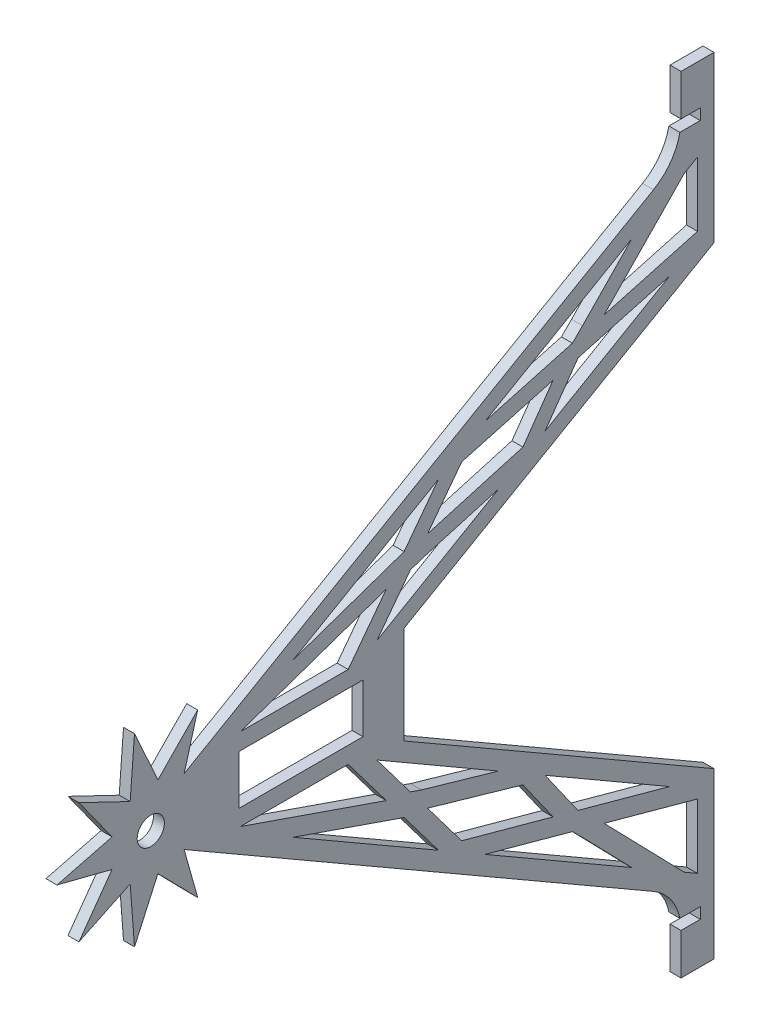
SolidWorks part; units mm, degrees
ref_plane "Front Plane" through (0, 0, 0) normal (1, 0, 0) x (0, 1, 0)
ref_plane "Top Plane" through (0, 0, 0) normal (0, 0, 1) x (0, 1, 0)
ref_plane "Right Plane" through (0, 0, 0) normal (0, 1, 0) x (-1, 0, 0)
sketch "Sketch1" plane through (0, 0, 0) normal (1, 0, 0) x (0, 1, 0)
  line L0 (-4.95, 0) -> (-129.0803, -215) construction
  line L1 (0, -4.95) -> (-121.2724, -215) construction
  line L2 (0, -4.95) -> (121.2724, -215) construction
  line L3 (4.95, 0) -> (129.0803, -215) construction
  line L4 (0, 0) -> (0, -215) construction
  line L5 (-129.0803, -215) -> (129.0803, -215) construction
  line L6 (0, 0) -> (0, -38.94) construction
  line L7 (0, -38.94) -> (0, -77.24) construction
  line L8 (-8.95, -32.14) -> (8.95, -32.14)
  line L9 (-8.95, -32.14) -> (-8.95, -77.24)
  line L10 (-8.95, -77.24) -> (8.95, -77.24)
  line L11 (8.95, -32.14) -> (8.95, -77.24)
  line L12 (-10.8997, -10.3052) -> (-129.0803, -215)
  line L13 (-129.0803, -215) -> (-88.6658, -215)
  line L14 (-88.6658, -215) -> (-17.7903, -92.24)
  line L15 (-17.7903, -92.24) -> (17.7903, -92.24)
  line L16 (17.7903, -92.24) -> (88.6658, -215)
  line L17 (88.6658, -215) -> (129.0803, -215)
  line L18 (129.0803, -215) -> (10.8997, -10.3052)
  circle A0 centre (0, 0) radius 4.95 construction
  circle A1 centre (0, 0) radius 7.5 construction
  arc A2 (-10.8997, -10.3052) -> (10.8997, -10.3052) centre (0, 0) cw
  circle A3 centre (0, 0) radius 4.95
  dimension "D2" = 9.9
  dimension "D3" = 15
  dimension "D9" = 15
  dimension "D10" = 35
  dimension "D1" = 215
  dimension "D4" = 60
  dimension "D5" = 38.94
  dimension "D6" = 45.1
  dimension "D7" = 17.9
  dimension "D8" = 6.8
  dimension "D11" = 35
  dimension "D12" = 15
extrude "Boss-Extrude1" add sketch "Sketch1" along normal blind 4
sketch "Sketch2" plane through (4, 0, 0) normal (1, 0, 0) x (0, 1, 0)
  line L1 (-129.0803, -215) -> (129.0803, -215)
  line L2 (-129.0803, -215) -> (-129.0803, -205)
  line L3 (-129.0803, -205) -> (129.0803, -205)
  line L4 (129.0803, -215) -> (129.0803, -205)
  dimension "D1" = 10
extrude "Cut-Extrude1" cut sketch "Sketch2" against normal through all both and the other way through all
sketch "Sketch3" plane through (4, 0, 0) normal (1, 0, 0) x (0, 0, -1)
  line L1 (205, -82.8923) -> (193, -82.8923)
  line L2 (205, -82.8923) -> (205, -142.8923)
  line L3 (205, -142.8923) -> (193, -142.8923)
  line L4 (193, -82.8923) -> (193, -142.8923)
  line L5 (205, 82.8923) -> (193, 82.8923)
  line L6 (205, 82.8923) -> (205, 142.8923)
  line L7 (205, 142.8923) -> (193, 142.8923)
  line L8 (193, 82.8923) -> (193, 142.8923)
  dimension "D1" = 12
  dimension "D2" = 12
  dimension "D3" = 60
  dimension "D4" = 60
extrude "Boss-Extrude2" add sketch "Sketch3" against normal blind 4
fillet "Fillet1" radius 20 2 edges at (2, 116.3786, -193) (2, -116.3786, -193)
sketch "Sketch4" plane through (4, 0, 0) normal (1, 0, 0) x (0, 0, -1)
  line L0 (-7.5, 12.9904) -> (-14.0954, 5.1303) construction
  line L1 (-14.0954, -5.1303) -> (-7.5, -12.9904) construction
  line L2 (-7.5, -12.9904) -> (2.6047, -14.7721) construction
  line L3 (2.6047, -14.7721) -> (11.4907, -9.6418) construction
  line L4 (11.4907, -9.6418) -> (15, 0) construction
  line L5 (15, 0) -> (11.4907, 9.6418) construction
  line L6 (11.4907, 9.6418) -> (2.6047, 14.7721) construction
  line L7 (2.6047, 14.7721) -> (-7.5, 12.9904) construction
  line L8 (-14.0954, 5.1303) -> (-14.0954, -5.1303) construction
  line L9 (15, 0) -> (0, 0) construction
  line L10 (0, 0) -> (-14.0954, -5.1303) construction
  line L11 (0, 0) -> (-14.0954, 5.1303) construction
  line L12 (-14.0954, -5.1303) -> (-34.138, 0)
  line L13 (-34.138, 0) -> (-14.0954, 5.1303)
  line L14 (0, 0) -> (-14.0954, 0)
  line L15 (-14.0954, 0) -> (-34.138, 0)
  line L16 (-14.0954, -5.1303) -> (-14.0954, 5.1303)
  circle A0 centre (0, 0) radius 14.0954 construction
  arc A1 (10.3052, 10.8997) -> (10.3052, -10.8997) centre (0, 0) ccw construction
  point P17 (-34.138, 0)
  arc M29 (10.3052, 10.8997) -> (10.3052, -10.8997) centre (0, 0) ccw
extrude "Boss-Extrude3" add sketch "Sketch4" against normal blind 4 contours L15 L13 M29 | L15 L12 M29 region at (4, -1.6958, 21.1835) region at (4, 1.6958, 21.1835)
ref_axis "Axis1" through (-0.2, 0, 0) along (1, 0, 0)
pattern_circular "CirPattern1" count 9 over 360 about axis through (-0.2, 0, 0) along (1, 0, 0) of "Boss-Extrude3"
sketch "Sketch5" plane through (4, 0, 0) normal (1, 0, 0) x (0, 0, -1)
  line L0 (205, -142.8923) -> (205, -82.8923) construction
  line L1 (200, -123.8923) -> (183, -123.8923)
  line L2 (200, -123.8923) -> (200, -127.8923)
  line L3 (200, -127.8923) -> (183, -127.8923)
  line L4 (183, -123.8923) -> (183, -127.8923)
  line L5 (193, -142.8923) -> (205, -142.8923) construction
  dimension "D1" = 5
  dimension "D2" = 22
  dimension "D3" = 15
  dimension "D4" = 4
extrude "Cut-Extrude2" cut sketch "Sketch5" against normal through all both and the other way through all
mirror "Mirror1" about plane through (0, 0, 0) normal (0, 1, 0) of "Cut-Extrude2"
sketch "Sketch6" plane through (4, 0, 0) normal (1, 0, 0) x (0, 1, 0)
  line L8 (-14.95, -75.6035) -> (-86.3564, -199)
  line L9 (-16.7578, -73.2093) -> (-15.4134, -72.1942)
  line L12 (-20.0419, -38.14) -> (-104.6051, -184.6077)
  line L18 (-40.452, -87.9788) -> (-41.913, -92.2033)
  line L19 (-16.7578, -73.2093) -> (-33.3206, -85.7154)
  line L20 (-68.2493, -121.6376) -> (-88.914, -196.9829)
  line L21 (-18.8134, -82.2798) -> (-34.9667, -94.4767)
  line L22 (-59.7005, -113.1525) -> (-68.825, -146.421)
  line L23 (-104.6051, -184.6077) -> (-112.9145, -199)
  line L24 (-102.2289, -186.4817) -> (-110.1106, -194.1434)
  line L25 (-88.914, -196.9829) -> (-89.4672, -199)
  line L26 (-102.2289, -186.4817) -> (-80.1463, -165.0151)
  line L27 (-68.3452, -153.4201) -> (-54.2342, -143.4901)
  line L28 (-44.4406, -126.5659) -> (-36.3741, -98.5461)
  line L29 (-27.9579, -51.8508) -> (-40.452, -87.9788)
  line L30 (-99.0996, -175.072) -> (-80.6727, -157.1591)
  line L31 (-68.825, -146.421) -> (-53.2438, -135.4564)
  line L32 (-53.2438, -135.4564) -> (-43.2459, -100.7281)
  line L33 (-19.1463, -44.7292) -> (-33.3206, -85.7154)
  line L34 (-20.0419, -38.14) -> (-14.95, -29.3407)
  line L35 (-36.3741, -98.5461) -> (-34.9667, -94.4767)
  line L36 (-68.3452, -153.4201) -> (-71.3184, -155.5124)
  line L37 (-80.6727, -157.1591) -> (-76.9784, -153.4648)
  line L38 (-71.3184, -155.5124) -> (-80.4428, -188.7809)
  line L39 (-41.913, -92.2033) -> (-58.4758, -104.7094)
  line L40 (-43.2459, -100.7281) -> (-59.7005, -113.1525)
  line L41 (-14.95, -75.6035) -> (-14.95, -29.3407)
  line L42 (-19.1463, -44.7292) -> (-14.95, -32.5951)
  line L43 (-15.4134, -72.1942) -> (-14.95, -71.8443)
  line L44 (-86.3564, -199) -> (-112.9145, -199)
extrude "Cut-Extrude3" cut sketch "Sketch6" against normal through all both and the other way through all contours L9 L43 L41 L42 L33 L19 | L39 L18 L29 L12 | L35 L28 L8 L21 | L32 L40 L22 L31 | L36 L38 L8 L27 | L30 L37 L20 L12 | L44 L25 L20 L26 L24 L23 region at (4, -32.8347, -101.1949) region at (4, -21.0735, -63.3849) region at (4, -68.6652, -162.5944) region at (4, -42.7822, -82.9212) region at (4, -94.6864, -187.5516) region at (4, -81.4577, -150.1016) region at (4, -56.1842, -123.8068)
fillet "Fillet2" [suppressed] radius 2
mirror "Mirror2" about plane through (0, 0, 0) normal (0, 1, 0) of "Cut-Extrude3"
